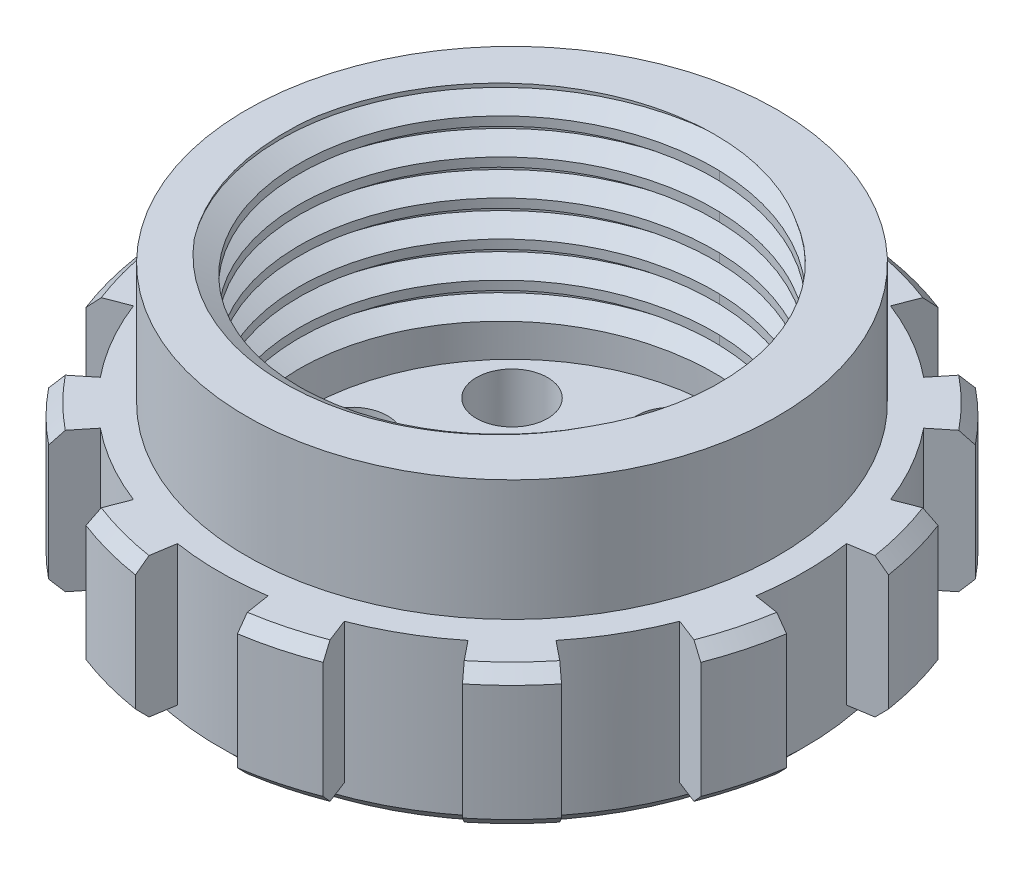
SolidWorks part; units mm, degrees
ref_plane "Front" through (0, 0, 0) normal (0, 0, 1) x (1, 0, 0)
ref_plane "Top" through (0, 0, 0) normal (0, 1, 0) x (1, 0, 0)
ref_plane "Right" through (0, 0, 0) normal (1, 0, 0) x (0, 0, -1)
sketch "Sketch1" plane through (0, 0, 0) normal (0, 0, 1) x (1, 0, 0)
  line L0 (0, 0) -> (0, 50.9403) construction
  line L1 (0, 0) -> (13.9, 0)
  line L2 (13.9, 0) -> (13.9, 6.9)
  line L3 (13.9, 6.9) -> (11.2, 6.9)
  line L4 (11.2, 6.9) -> (11.2, 12)
  line L5 (11.2, 12) -> (8.75, 12)
  line L6 (8.75, 12) -> (8.75, 2.3)
  line L7 (8.75, 2.3) -> (0, 2.3)
  line L8 (0, 2.3) -> (0, 0)
  dimension "D1" = 27.8
  dimension "D2" = 6.9
  dimension "D3" = 22.4
  dimension "D4" = 12
  dimension "D5" = 17.5
  dimension "D6" = 9.7
revolve "Revolve1" add sketch "Sketch1" angle 360 about L0
sketch "Sketch2" plane through (0, 2.3, 0) normal (0, 1, 0) x (1, 0, 0)
  circle A0 centre (0, 0) radius 3.5
  circle A1 centre (6.75, 0) radius 1.5
  point P5 (0, 0)
  dimension "D1" = 7
  dimension "D2" = 3
  dimension "D3" = 6.75
extrude "Cut-Extrude1" cut sketch "Sketch2" against normal blind 10
pattern_circular "CirPattern1" count 8 over 360 about axis through (0, 12, 0) along (0, -1, 0) of "Cut-Extrude1"
chamfer "Chamfer1" distance 0.5 angle 45 1 edges at (0, 6.9, -13.9)
sketch "Sketch3" plane through (0, 0, 0) normal (0, -1, 0) x (1, 0, 0)
  line L0 (12.35, 0) -> (15.2865, 0) construction
  line L6 (13.7327, 2.15) -> (12.2014, 1.9103)
  line L7 (12.2014, -1.9103) -> (13.7327, -2.15)
  arc A0 (13.7327, -2.15) -> (13.7327, 2.15) centre (0, 0) ccw
  arc A1 (12.2014, -1.9103) -> (12.2014, 1.9103) centre (0, 0) ccw
  dimension "D3" = 24.7
extrude "Cut-Extrude2" cut sketch "Sketch3" against normal blind 10
pattern_circular "CirPattern2" count 12 over 360 about axis through (0, 0, 0) along (0, -1, 0) of "Cut-Extrude2"
sketch "Sketch4" plane through (0, 0, 0) normal (0, -1, 0) x (1, 0, 0)
  circle A0 centre (0, 0) radius 13.9
  circle A1 centre (0, 0) radius 12.35
extrude "Cut-Extrude3" cut sketch "Sketch4" against normal blind 1
chamfer "Chamfer2" distance 0.5 angle 45 13 edges at (0, 0, -12.35) (-13.4264, 1, -3.5976) (-9.8288, 1, -9.8288) (-3.5976, 1, -13.4264) (3.5976, 1, -13.4264) (9.8288, 1, -9.8288) (13.4264, 1, -3.5976) (13.4264, 1, 3.5976) (9.8288, 1, 9.8288) (-13.4264, 1, 3.5976) (-9.8288, 1, 9.8288) (-3.5976, 1, 13.4264) (3.5976, 1, 13.4264)
thread "Thread1" pitch 1.5 method cut profile "Thread Profile1" start angle 0, offset 2, length 10, pitch 1.5, diameter 17.5
ref_plane "Plane1" through (-8.75, 14, 0) normal (0, 0, 1) x (-1, 0, 0)
sketch "Thread Profile1" plane through (-8.75, 14, 0) normal (0, 0, 1) x (-1, 0, 0)
  line L0 (0, 0) -> (0, 1.5) construction
  line L1 (0, 0) -> (0.8119, 0.4687)
  line L2 (0.8119, 0.4687) -> (0.8119, 0.6562)
  line L3 (0.8119, 0.6562) -> (0, 1.125)
  line L4 (0.8119, 0.5625) -> (0, 0.5625) construction
  line L11 (0, 0) -> (0, 1.125)
  point P2 (0, 0)
  dimension "Pitch" = 1.5
  dimension "Profile_Angle" = 60
  dimension "Profile_Land" = 0.1875
  dimension "Profile_Height" = 0.8119
